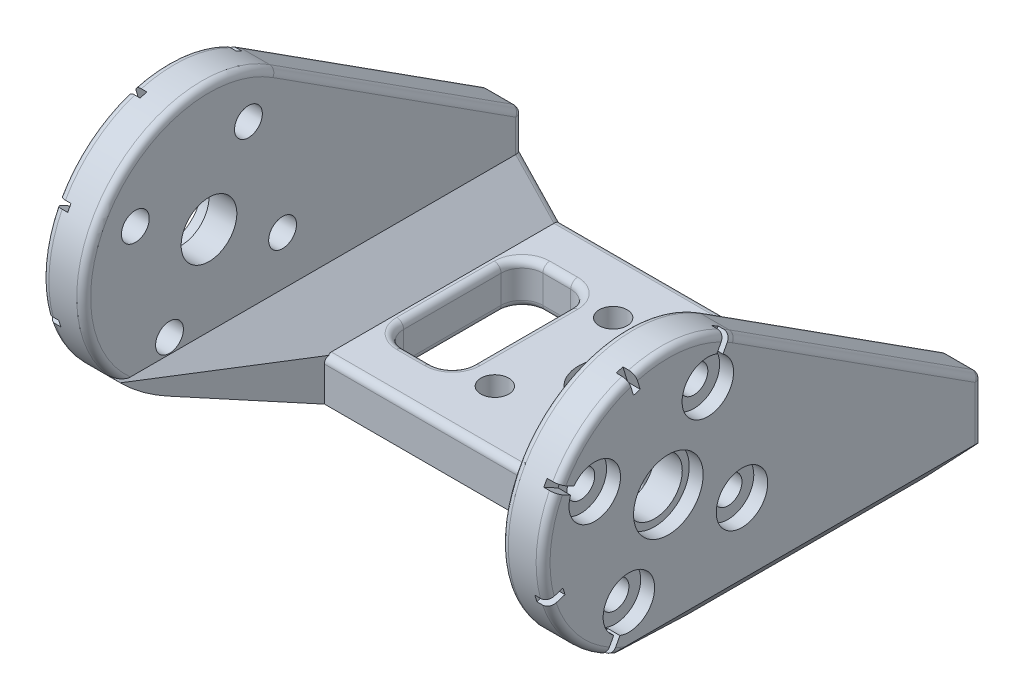
SolidWorks part; units mm, degrees
material "ABS"
ref_plane "Front Plane" through (0, 0, 0) normal (0, 0, 1) x (1, 0, 0)
ref_plane "Top Plane" through (0, 0, 0) normal (0, 1, 0) x (1, 0, 0)
ref_plane "Right Plane" through (0, 0, 0) normal (1, 0, 0) x (0, 0, -1)
sketch "Sketch4" plane through (0, 0, 0) normal (1, 0, 0) x (0, 0, -1)
  line L0 (-8.5, 0) -> (8.5, 0)
  line L1 (8.5, 0) -> (8.5, 8.5)
  line L2 (-8.5, 0) -> (-17.6554, 4.0222)
  line L3 (-9.1764, 19.8377) -> (8.5, 8.5)
  arc A0 (-17.6554, 4.0222) -> (-9.1764, 19.8377) centre (-14.0355, 12.2621) cw
  dimension "D3" = 9
  dimension "D1" = 8.5
  dimension "D2" = 21
  dimension "D5" = 17
  dimension "D6" = 10
extrude "Boss-Extrude2" add sketch "Sketch4" along normal mid plane 36
fillet "Fillet1" radius 0.5 13 edges at (-18, 2.0111, 13.0777) (-18, 16.5146, 21.9674) (0, 0, 8.5) (-18, 0, 0) (-18, 14.1689, 0.3382) (0, 0, -8.5) (0, 8.5, -8.5) (-18, 4.25, -8.5) (18, 16.5146, 21.9674) (18, 14.1689, 0.3382) (18, 4.25, -8.5) (18, 0, 0) (18, 2.0111, 13.0777)
ref_plane "Plane2" through (0, 3, 0) normal (0, 1, 0) x (1, 0, 0)
sketch "Sketch5" plane through (0, 3, 0) normal (0, 1, 0) x (1, 0, 0)
  line L0 (-17.5, 8.5) -> (17.5, 8.5) construction
  line L1 (12.25, -8.5) -> (-12.25, -8.5)
  line L2 (12.25, -8.5) -> (12.25, 8.5)
  line L3 (12.25, 8.5) -> (-12.25, 8.5)
  line L4 (-12.25, -8.5) -> (-12.25, 8.5)
  line L5 (12.25, -8.5) -> (-12.25, 8.5) construction
  line L6 (12.25, 8.5) -> (-12.25, -8.5) construction
  point P0 (0, 0)
  point P7 (0, 8.5)
  dimension "D1" = 24.5
  dimension "D2" = 17
extrude "Cut-Extrude1" cut sketch "Sketch5" along normal through all
sketch "Sketch6" plane through (0, 0, 0) normal (0, 1, 0) x (1, 0, 0)
  line L0 (-12.25, -8.5) -> (12.25, -8.5) construction
  line L1 (-12.25, -8.5) -> (12.25, -8.5)
  line L2 (-12.25, -8.5) -> (-12.25, -23.0355)
  line L3 (-17.5, -23.0355) -> (17.5, -23.0355) construction
  line L4 (-12.25, -23.0355) -> (12.25, -23.0355)
  line L5 (12.25, -23.0355) -> (12.25, -8.5)
extrude "Cut-Extrude2" cut sketch "Sketch6" along normal through all
sketch "Sketch8" plane through (0, 0, 0) normal (0, 0, 1) x (1, 0, 0)
  line L0 (-15, 21.2621) -> (-15, 5.9047)
  line L1 (-12.25, 8.6476) -> (-12.25, 19.8377) construction
  line L2 (-12.25, 8.6476) -> (-12.25, 19.8377)
  line L3 (-18, 19.4168) -> (-18, 8.2267) construction
  line L4 (-12.25, 21.2621) -> (-17.5, 21.2621) construction
  line L5 (-15, 21.2621) -> (-12.25, 21.2621)
  line L6 (-12.25, 21.2621) -> (-12.25, 19.8377)
  line L7 (-15, 5.9047) -> (-12.25, 3)
  line L8 (17.3445, 3) -> (-17.3445, 3) construction
  line L9 (-12.25, 3) -> (-12.25, 8.6476)
  line L10 (-13.875, 0) -> (-18, 0)
  line L11 (-17.5, 0) -> (17.5, 0) construction
  line L15 (-18, 0) -> (-18, 4.3571)
  line L16 (-18, 8.2267) -> (-18, 0.5) construction
  line L17 (-18, 4.3571) -> (-13.875, 0)
  line L18 (0, -999.5) -> (0, 49000.5) construction
  line L19 (17.5, 0.5) -> (-17.5, 0.5) construction
  line L20 (18, 4.3571) -> (13.875, 0)
  line L21 (18, 0) -> (18, 4.3571)
  line L22 (13.875, 0) -> (18, 0)
  line L23 (12.25, 3) -> (12.25, 8.6476)
  line L24 (15, 5.9047) -> (12.25, 3)
  line L25 (12.25, 21.2621) -> (12.25, 19.8377)
  line L26 (15, 21.2621) -> (12.25, 21.2621)
  line L27 (12.25, 8.6476) -> (12.25, 19.8377)
  line L28 (15, 21.2621) -> (15, 5.9047)
  point P26 (0, 0.5)
  dimension "D1" = 3
  dimension "D2" = 4
  dimension "D3" = 6
extrude "Cut-Extrude3" cut sketch "Sketch8" against normal through all both and the other way through all
sketch "Sketch9" plane through (0, 3, 0) normal (0, 1, 0) x (1, 0, 0)
  line L0 (-12.25, -8.5) -> (-15, -20.406)
  line L1 (-15, -20.406) -> (-12.25, -20.406)
  line L2 (-12.25, -20.406) -> (-12.25, -8.5)
  line L3 (0, -1000) -> (0, 49000) construction
  line L4 (12.25, -20.406) -> (12.25, -8.5)
  line L5 (15, -20.406) -> (12.25, -20.406)
  line L6 (12.25, -8.5) -> (15, -20.406)
extrude "Cut-Extrude4" cut sketch "Sketch9" against normal through all both and the other way through all
fillet "Fillet2" radius 0.5 12 edges at (-15, 17.9098, 21.0428) (-15, 7.0657, -8.5) (-15, 8.4665, -8.4387) (15, 17.9098, 21.0428) (15, 14.2426, 0.4532) (15, 8.4665, -8.4387) (-13.625, 4.4524, -8.5) (-15, 14.2426, 0.4532) (0, 3, -8.5) (0, 3, 8.5) (15, 7.0657, -8.5) (13.625, 4.4524, -8.5)
sketch "Sketch10" plane through (0, 3, 0) normal (0, 1, 0) x (1, 0, 0)
  line L0 (-11.55, -3.5) -> (-11.55, 3.5)
  line L1 (-10.05, 5) -> (-8.05, 5)
  line L2 (-6.55, 3.5) -> (-6.55, -3.5)
  line L3 (-8.05, -5) -> (-10.05, -5)
  line L4 (-12.25, 8) -> (-12.25, -8) construction
  line L5 (0, -1000) -> (0, 49000) construction
  line L6 (-4.25, -4.25) -> (-4.25, 4.25) construction
  line L7 (4.25, -4.25) -> (4.25, 4.25) construction
  line L8 (8.05, -5) -> (10.05, -5)
  line L9 (6.55, 3.5) -> (6.55, -3.5)
  line L10 (10.05, 5) -> (8.05, 5)
  line L11 (11.55, -3.5) -> (11.55, 3.5)
  arc A0 (-11.55, 3.5) -> (-10.05, 5) centre (-10.05, 3.5) cw
  arc A1 (-8.05, 5) -> (-6.55, 3.5) centre (-8.05, 3.5) cw
  arc A2 (-6.55, -3.5) -> (-8.05, -5) centre (-8.05, -3.5) cw
  arc A3 (-10.05, -5) -> (-11.55, -3.5) centre (-10.05, -3.5) cw
  circle A4 centre (0, 0) radius 2
  circle A5 centre (-4.25, -4.25) radius 1
  circle A6 centre (-4.25, 4.25) radius 1
  circle A7 centre (4.25, 4.25) radius 1
  circle A8 centre (4.25, -4.25) radius 1
  arc A9 (10.05, -5) -> (11.55, -3.5) centre (10.05, -3.5) ccw
  arc A10 (6.55, -3.5) -> (8.05, -5) centre (8.05, -3.5) ccw
  arc A11 (8.05, 5) -> (6.55, 3.5) centre (8.05, 3.5) ccw
  arc A12 (11.55, 3.5) -> (10.05, 5) centre (10.05, 3.5) ccw
  point P18 (-6.55, 0)
  point P24 (-4.25, 0)
  dimension "D4" = 4
  dimension "D5" = 2
  dimension "D6" = 1.5
  dimension "D1" = 7
  dimension "D2" = 2
  dimension "D3" = 0.7
  dimension "D7" = 8.5
  dimension "D8" = 8.5
extrude "Cut-Extrude5" cut sketch "Sketch10" against normal through all
fillet "Fillet3" radius 0.5 24 edges at (-9.05, 0, -5) (-6.9893, 0, -4.5607) (-6.55, 0, 0) (-6.9893, 0, 4.5607) (-9.05, 0, 5) (-11.1107, 0, 4.5607) (-11.55, 0, 0) (-9.05, 3, -5) (-6.9893, 3, -4.5607) (-6.55, 3, 0) (-6.9893, 3, 4.5607) (-9.05, 3, 5) (-11.1107, 3, 4.5607) (-11.55, 3, 0) (9.05, 3, -5) (11.1107, 3, -4.5607) (11.55, 3, 0) (11.1107, 3, 4.5607) (9.05, 3, 5) (6.9893, 3, 4.5607) (6.55, 3, 0) (-11.1107, 0, -4.5607) (-11.1107, 3, -4.5607) (6.9893, 3, -4.5607)
sketch "Sketch11" plane through (0, 3, 0) normal (0, 1, 0) x (1, 0, 0)
  circle A0 centre (0, 0) radius 2.5
  dimension "D1" = 5
extrude "Cut-Extrude6" cut sketch "Sketch11" against normal blind 0.8
sketch "Sketch12" plane through (18, 0, 0) normal (1, 0, 0) x (0, 0, -1)
  line L1 (-6.1035, 8.0096) -> (-21.9674, 16.5146) construction
  line L2 (-10.0192, 19.7534) -> (-18.0517, 4.7708) construction
  circle A0 centre (-14.0355, 12.2621) radius 6 construction
  circle A1 centre (-14.0355, 12.2621) radius 2
  circle A2 centre (-19.3234, 15.0971) radius 1
  arc A3 (-9.1764, 19.8377) -> (-17.6554, 4.0222) centre (-14.0355, 12.2621) ccw construction
  arc A4 (-9.4464, 19.4168) -> (-17.4543, 4.48) centre (-14.0355, 12.2621) ccw construction
  circle A5 centre (-11.2005, 17.5501) radius 1
  circle A6 centre (-8.7475, 9.4271) radius 1
  circle A7 centre (-16.8704, 6.9741) radius 1
  point P8 (-14.0355, 12.2621)
  point P14 (-14.0355, 12.2621)
  point P20 (-14.0355, 12.2621)
  dimension "D1" = 12
  dimension "D2" = 4
  dimension "D3" = 2
extrude "Cut-Extrude7" cut sketch "Sketch12" against normal up to next
sketch "Sketch13" plane through (18, 0, 0) normal (1, 0, 0) x (0, 0, -1)
  circle A0 centre (-14.0355, 12.2621) radius 2 construction
  circle A1 centre (-14.0355, 12.2621) radius 2
  circle A2 centre (-14.0355, 12.2621) radius 2.5
  circle A3 centre (-8.7475, 9.4271) radius 1 construction
  circle A4 centre (-16.8704, 6.9741) radius 1 construction
  circle A5 centre (-11.2005, 17.5501) radius 1 construction
  circle A6 centre (-19.3234, 15.0971) radius 1 construction
  circle A7 centre (-8.7475, 9.4271) radius 1
  circle A8 centre (-16.8704, 6.9741) radius 1
  circle A9 centre (-11.2005, 17.5501) radius 1
  circle A10 centre (-19.3234, 15.0971) radius 1
  circle A11 centre (-19.3234, 15.0971) radius 1.85
  circle A12 centre (-11.2005, 17.5501) radius 1.85
  circle A13 centre (-8.7475, 9.4271) radius 1.85
  circle A14 centre (-16.8704, 6.9741) radius 1.85
  dimension "D1" = 5
  dimension "D2" = 3.7
extrude "Cut-Extrude8" cut sketch "Sketch13" against normal blind 1
sketch "Sketch14" plane through (18, 0, 0) normal (1, 0, 0) x (0, 0, -1)
  line L0 (-14.0355, 12.2621) -> (-19.3234, 15.0971) construction
  line L1 (-14.0355, 12.2621) -> (-10.0192, 19.7534) construction
  line L2 (-14.0355, 12.2621) -> (-14468.4628, 47877.3802) construction
  line L3 (-14.0355, 12.2621) -> (-47879.1536, -14442.1652) construction
  line L4 (-21.0571, 15.7428) -> (-22.1147, 16.3098)
  line L5 (-22.1147, 16.3098) -> (-21.8784, 16.7505)
  line L6 (-21.8784, 16.7505) -> (-20.8208, 16.1835)
  line L7 (-20.8208, 16.1835) -> (-21.0571, 15.7428)
  line L8 (-16.5392, 19.6884) -> (-16.8861, 20.8372)
  line L9 (-16.8861, 20.8372) -> (-16.4075, 20.9817)
  line L10 (-16.4075, 20.9817) -> (-16.0606, 19.8329)
  line L11 (-16.0606, 19.8329) -> (-16.5392, 19.6884)
  line L12 (-10.5547, 19.2837) -> (-9.9877, 20.3413)
  line L13 (-9.9877, 20.3413) -> (-9.547, 20.1051)
  line L14 (-9.547, 20.1051) -> (-10.114, 19.0475)
  line L15 (-10.114, 19.0475) -> (-10.5547, 19.2837)
  line L16 (-6.6091, 14.7659) -> (-5.4604, 15.1128) [skipped]
  line L17 (-5.4604, 15.1128) -> (-5.3158, 14.6341) [skipped]
  line L18 (-5.3158, 14.6341) -> (-6.4646, 14.2872) [skipped]
  line L19 (-6.4646, 14.2872) -> (-6.6091, 14.7659) [skipped]
  line L20 (-7.0138, 8.7813) -> (-5.9562, 8.2143) [skipped]
  line L21 (-5.9562, 8.2143) -> (-6.1925, 7.7737) [skipped]
  line L22 (-6.1925, 7.7737) -> (-7.2501, 8.3407) [skipped]
  line L23 (-7.2501, 8.3407) -> (-7.0138, 8.7813) [skipped]
  line L24 (-11.5317, 4.8358) -> (-11.1848, 3.687) [skipped]
  line L25 (-11.1848, 3.687) -> (-11.6634, 3.5425) [skipped]
  line L26 (-11.6634, 3.5425) -> (-12.0103, 4.6912) [skipped]
  line L27 (-12.0103, 4.6912) -> (-11.5317, 4.8358) [skipped]
  line L28 (-17.5162, 5.2405) -> (-18.0832, 4.1829)
  line L29 (-18.0832, 4.1829) -> (-18.5239, 4.4191)
  line L30 (-18.5239, 4.4191) -> (-17.9569, 5.4767)
  line L31 (-17.9569, 5.4767) -> (-17.5162, 5.2405)
  line L32 (-21.4618, 9.7583) -> (-22.6105, 9.4114)
  line L33 (-22.6105, 9.4114) -> (-22.7551, 9.8901)
  line L34 (-22.7551, 9.8901) -> (-21.6063, 10.237)
  line L35 (-21.6063, 10.237) -> (-21.4618, 9.7583)
  circle A0 centre (-14.0355, 12.2621) radius 2.5 construction
  circle A1 centre (-14.0355, 12.2621) radius 2.5 construction
  circle A5 centre (-19.3234, 15.0971) radius 1.85 construction
  circle A6 centre (-19.3234, 15.0971) radius 1.85 construction
  point P16 (-20.939, 15.9632)
  point P21 (-16.2999, 19.7607)
  point P22 (-10.3344, 19.1656)
  dimension "D1" = 45
  dimension "D2" = 1.2
  dimension "D3" = 0.5
  dimension "D5" = 45
  dimension "D6" = 7.833
  dimension "D4" = 8
extrude "Cut-Extrude9" cut sketch "Sketch14" against normal blind 0.9
mirror "Mirror1" about plane through (0, 0, 0) normal (1, 0, 0) of "Cut-Extrude8", "Cut-Extrude9", "Cut-Extrude7"
sketch "Sketch15" plane through (0, 0, -8.5) normal (0, 0, -1) x (-1, 0, 0)
  line L0 (-0.25, 0) -> (-0.25, 3)
  line L1 (13.875, 0) -> (-13.875, 0) construction
  line L2 (17.3445, 3) -> (-17.3445, 3) construction
  line L3 (-0.25, 3) -> (0.25, 3)
  line L4 (0.25, 3) -> (0.25, 0)
  line L5 (0.25, 0) -> (-0.25, 0)
  point P6 (0, 0)
  dimension "D1" = 0.5
extrude "Cut-Extrude10" cut sketch "Sketch15" against normal blind 0.3
